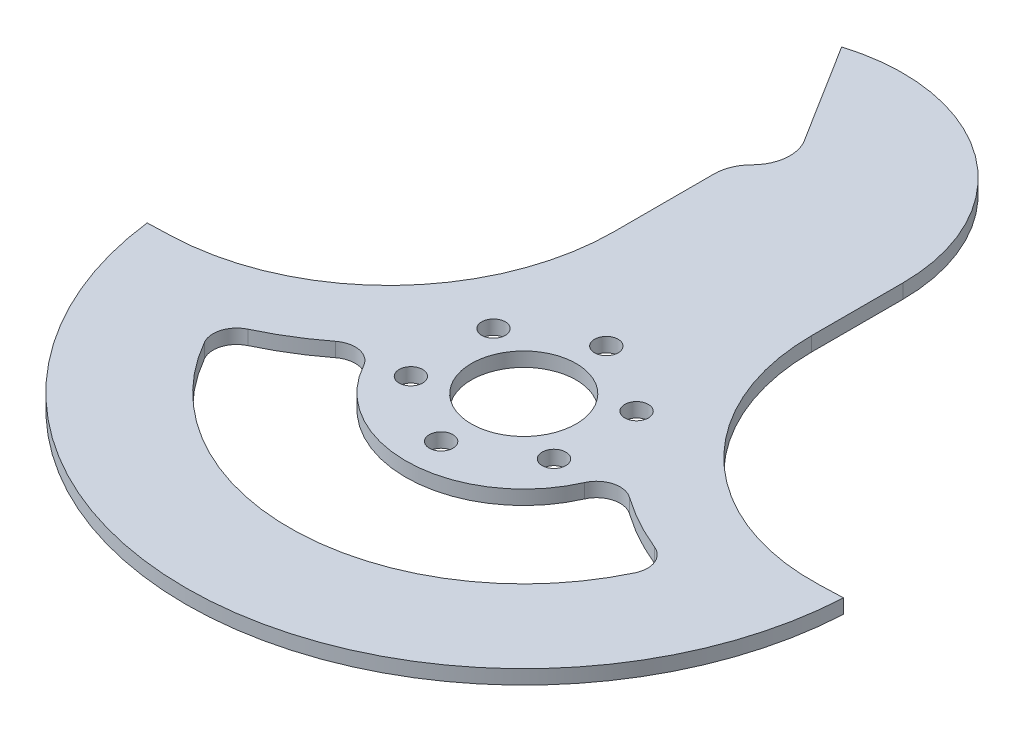
SolidWorks part; units mm, degrees
ref_plane "Front Plane" through (0, 0, 0) normal (0, 0, 1) x (1, 0, 0)
ref_plane "Top Plane" through (0, 0, 0) normal (0, 1, 0) x (1, 0, 0)
ref_plane "Right Plane" through (0, 0, 0) normal (1, 0, 0) x (0, 0, -1)
other "Center of Mass"
sketch "Sketch1" plane through (0, 0, 0) normal (0, 1, 0) x (1, 0, 0)
  line L0 (0, 0) -> (-23040.0357, 36803.9862) construction
  line L1 (0, -1000) -> (0, 49000) construction
  line L2 (-29.7853, 97.136) -> (-16.5198, 75.9457)
  line L3 (18.7342, 112.0138) -> (41531.855, 12841.4067) construction
  line L4 (-20, 60.3286) -> (20, 60.3286) construction
  line L5 (-20, 60.3286) -> (-20, 39.1549)
  line L6 (20, 60.3286) -> (20, 40.9875)
  line L7 (0, 0) -> (-71.0663, -8.7258) construction
  line L8 (0, 0) -> (71.5019, -3.7473) construction
  line L9 (-71.0663, -8.7258) -> (71.5019, -3.7473) construction
  line L10 (-71.0663, -8.7258) -> (-66.0694, -8.5513)
  line L11 (71.5019, -3.7473) -> (66.5049, -3.9218)
  line L12 (-28.8426, 54.8122) -> (35326.4965, 35410.1512) construction
  circle A0 centre (0, 0) radius 101.6 construction
  arc A1 (-16.5198, 75.9457) -> (-17.6481, 66.0067) centre (-23.3262, 71.6848) cw
  arc A2 (-17.6481, 66.0067) -> (-20, 60.3286) centre (-11.97, 60.3286) ccw
  arc A3 (-29.7853, 97.136) -> (20, 60.3286) centre (-18.4989, 60.3286) cw
  circle A4 centre (0, 0) radius 71.6 construction
  arc A5 (-71.0663, -8.7258) -> (71.5019, -3.7473) centre (0, 0) ccw
  arc A6 (-66.0694, -8.5513) -> (-20, 39.1549) centre (-67.7353, 39.1549) ccw
  arc A7 (20, 40.9875) -> (66.5049, -3.9218) centre (64.9367, 40.9875) ccw
  circle A8 centre (0, 0) radius 30.5026 construction
  point P9 (0, 60.3286)
  point P20 (0, -71.6)
  point P21 (0, -101.6)
  point P31 (2.4988, -71.5564)
  point P34 (-15.2961, 71.6848)
  dimension "D1" = 203.2
  dimension "D2" = 75
  dimension "D3" = 25
  dimension "D4" = 40
  dimension "D5" = 30
  dimension "D6" = 92
  dimension "D7" = 170
  dimension "D8" = 5
  dimension "D9" = 45
extrude "Boss-Extrude1" add sketch "Sketch1" along normal blind 3.02
sketch "Sketch6" plane through (0, 3.02, 0) normal (0, 1, 0) x (1, 0, 0)
  line L0 (-41.0794, -17.6358) -> (-47.4528, -4.0572) construction
  line L1 (29.2213, -7.1458) -> (38.1596, 4.9002) construction
  arc A0 (-45.5884, -19.5412) -> (46.8909, -16.168) centre (0, 0) ccw
  arc A1 (-16.623, 2.7783) -> (-45.5884, -19.5412) centre (-67.7353, 39.1549) cw
  arc A2 (14.252, 8.9958) -> (46.8909, -16.168) centre (64.9367, 40.9875) ccw
  arc A3 (-16.623, 2.7783) -> (14.252, 8.9958) centre (0, 0) ccw
  arc A4 (-66.0694, -8.5513) -> (-20, 39.1549) centre (-67.7353, 39.1549) ccw construction
  arc A5 (-71.0663, -8.7258) -> (71.5019, -3.7473) centre (0, 0) ccw construction
  arc A6 (20, 40.9875) -> (66.5049, -3.9218) centre (64.9367, 40.9875) ccw construction
  circle A7 centre (0, 0) radius 30.5026 construction
  point P23 (0, -49.6)
  dimension "D1" = 22
  dimension "D2" = 15
extrude "Cut-Extrude2" cut sketch "Sketch6" against normal through all
fillet "Fillet6" radius 5 2 edges at (46.8909, 1.51, 16.168) (-45.5884, 1.51, 19.5412)
sketch "Sketch7" plane through (0, 3.02, 0) normal (0, 1, 0) x (1, 0, 0)
  circle A0 centre (0, 0) radius 25
  dimension "D1" = 50
extrude "Boss-Extrude5" add sketch "Sketch7" against normal up to surface (3.02 mm away) up to face at (0.9289, 0, 19.6333)
fillet "Fillet7" radius 5 2 edges at (24.7558, 1.51, 3.486) (-24.2527, 1.51, 6.0666)
sketch "Sketch8" plane through (0, 3.02, 0) normal (0, 1, 0) x (1, 0, 0)
  circle A0 centre (0.1682, -0.1726) radius 11.1
  point P2 (0, 0)
  dimension "D1" = 22.2
extrude "Cut-Extrude3" cut sketch "Sketch8" against normal through all
sketch "Sketch10" plane through (0, 3.02, 0) normal (0, 1, 0) x (1, 0, 0)
  circle A0 centre (0.1682, -17.6726) radius 7.3266 construction
  circle A1 centre (0, 0) radius 25 construction
  circle A3 centre (0.1682, -17.6726) radius 2.5
  circle A4 centre (-14.9873, -8.9226) radius 2.5
  circle A5 centre (-14.9873, 8.5774) radius 2.5
  circle A6 centre (0.1682, 17.3274) radius 2.5
  circle A7 centre (15.3236, 8.5774) radius 2.5
  circle A8 centre (15.3236, -8.9226) radius 2.5
  point P21 (0.1682, -0.1726)
  dimension "D1" = 5
  dimension "D3" = 35
  dimension "D2" = 6
extrude "Cut-Extrude4" cut sketch "Sketch10" against normal through all
sketch "Sketch11" plane through (0, 0, 0) normal (0, 1, 0) x (1, 0, 0)
  circle A0 centre (0.1682, -0.1726) radius 101.8143 construction
  circle A1 centre (0.1682, -0.1726) radius 11.1 construction
  circle A2 centre (0.1682, -0.1726) radius 71.7461 construction
ref_axis "Axis1" through (0.1682, 0, 0.1726) along (0, 1, 0)
